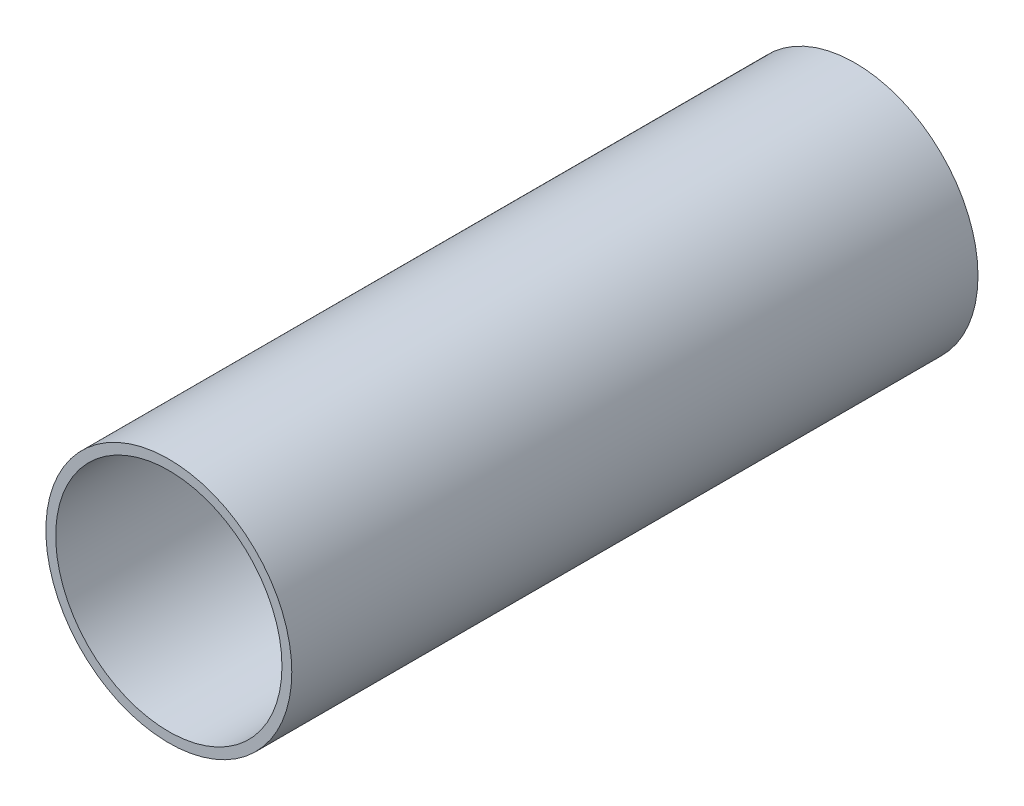
SolidWorks part; units mm, degrees
material "Thornel Mat VMA"
ref_plane "Front Plane" through (0, 0, 0) normal (0, 0, 1) x (1, 0, 0)
ref_plane "Top Plane" through (0, 0, 0) normal (0, 1, 0) x (1, 0, 0)
ref_plane "Right Plane" through (0, 0, 0) normal (1, 0, 0) x (0, 0, -1)
sketch "Sketch1" plane through (0, 0, 0) normal (0, 0, 1) x (1, 0, 0)
  circle A0 centre (0, 0) radius 25
  circle A1 centre (0, 0) radius 23
  dimension "D1" = 50
  dimension "D2" = 46
extrude "Boss-Extrude1" add sketch "Sketch1" along normal blind 39.5 and the other way blind 100
